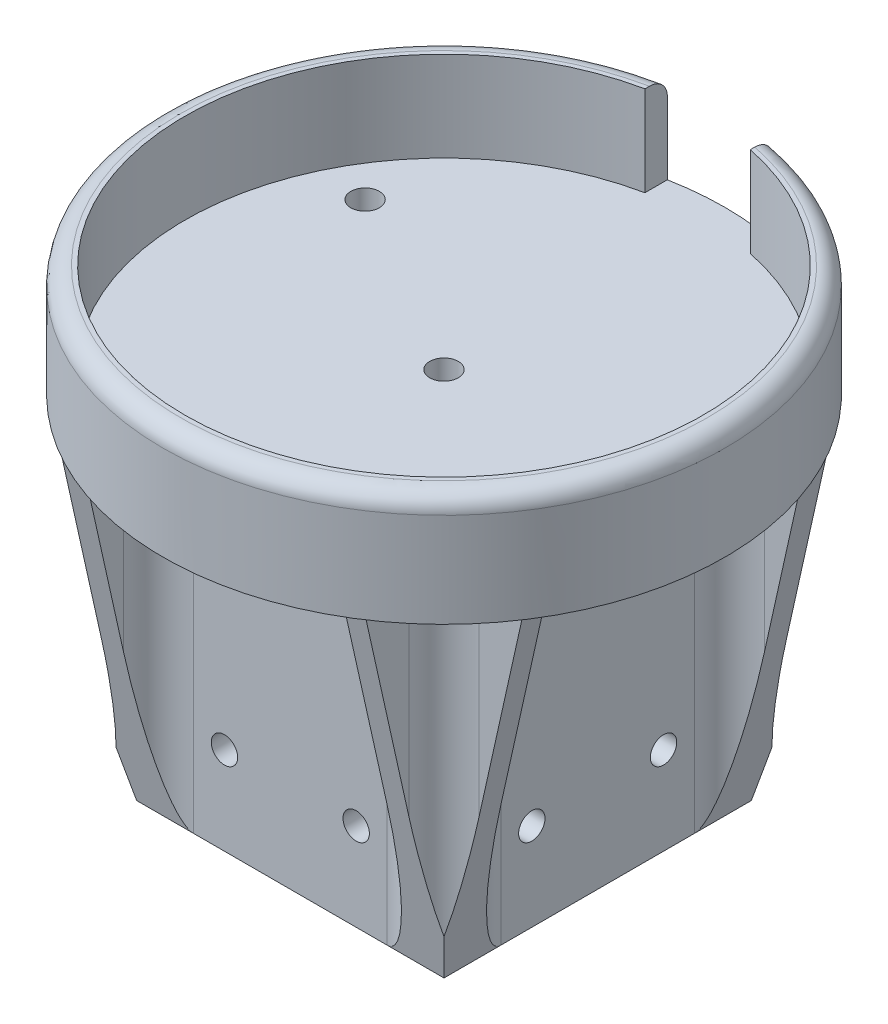
SolidWorks part; units mm, degrees
ref_plane "前视基准面" through (0, 0, 0) normal (0, 0, 1) x (1, 0, 0)
ref_plane "上视基准面" through (0, 0, 0) normal (0, 1, 0) x (1, 0, 0)
ref_plane "右视基准面" through (0, 0, 0) normal (1, 0, 0) x (0, 0, -1)
sketch "草图2" plane through (0, 0, 0) normal (0, 0, 1) x (1, 0, 0)
  line L0 (-64, 5) -> (-64, 21.5)
  line L1 (0, 0) -> (-64, 0)
  line L2 (0, 0) -> (0, 5)
  line L3 (0, 5) -> (-59, 5)
  line L4 (-64, 0) -> (-64, 5)
  line L5 (-60, 25.5) -> (-59, 25.5)
  line L6 (-59, 25.5) -> (-59, 5)
  arc A0 (-64, 21.5) -> (-60, 25.5) centre (-60, 21.5) cw
  point P10 (-64, 25.5)
  dimension "D7" = 4
  dimension "D1" = 5
  dimension "D2" = 20.5
  dimension "D3" = 5
  dimension "D4" = 5
  dimension "D5" = 59
  dimension "D6" = 5
revolve "旋转1" add sketch "草图2" angle 360 about L2
sketch "草图3" plane through (0, 0, 0) normal (0, -1, 0) x (1, 0, 0)
  line L6 (-35, -35) -> (35, -35)
  line L44 (-35, -35) -> (-35, 35)
  line L45 (-35, 35) -> (35, 35)
  line L69 (35, -35) -> (35, 35)
  line L70 (-35, -35) -> (35, 35) construction
  line L71 (-35, 35) -> (35, -35) construction
  point P1 (0, 0)
  dimension "D1" = 70
  dimension "D2" = 70
extrude "凸台-拉伸2" add sketch "草图3" along normal blind 80
sketch "草图5" plane through (0, -80, 0) normal (0, -1, 0) x (1, 0, 0)
  line L1 (-30, -30) -> (30, -30)
  line L2 (-30, -30) -> (-30, 30)
  line L3 (-30, 30) -> (30, 30)
  line L4 (30, -30) -> (30, 30)
  line L5 (-30, -30) -> (30, 30) construction
  line L6 (-30, 30) -> (30, -30) construction
  point P0 (0, 0)
  dimension "D1" = 60
  dimension "D2" = 60
extrude "切除-拉伸2" cut sketch "草图5" against normal blind 80
sketch "草图6" plane through (0, 5, 0) normal (0, 1, 0) x (1, 0, 0)
  circle A0 centre (0, 0) radius 3.25
  circle A1 centre (0, -49.1) radius 3.25
  circle A4 centre (-42.5218, 24.55) radius 3.25
  circle A5 centre (42.5218, 24.55) radius 3.25
  point P11 (1.5088, -2.6133)
  point P12 (0, 0)
  dimension "D1" = 6.5
  dimension "D2" = 6.5
  dimension "D3" = 49.1
extrude "切除-拉伸3" cut sketch "草图6" against normal blind 80
sketch "草图7" plane through (0, 0, 35) normal (0, 0, 1) x (1, 0, 0)
  line L0 (-35, -80) -> (-35, 0) construction
  line L1 (35, -80) -> (-35, -80) construction
  line L2 (35, 0) -> (-35, 0) construction
  line L3 (0, -58.025) -> (0, 58.025) construction
  circle A0 centre (-15, -60) radius 3
  circle A1 centre (-15, -15) radius 3
  circle A2 centre (15, -15) radius 3
  circle A3 centre (15, -60) radius 3
  point P6 (0, 0)
  dimension "D1" = 6
  dimension "D2" = 6
  dimension "D3" = 20
  dimension "D4" = 20
  dimension "D5" = 20
  dimension "D6" = 15
extrude "切除-拉伸4" cut sketch "草图7" against normal through all both and the other way through all
sketch "草图13" plane through (0, 0, -35) normal (0, 0, -1) x (-1, 0, 0)
  line L0 (-35, -80) -> (-52.8448, 0)
  line L1 (-64, 0) -> (64, 0) construction
  point P5 (-52.8448, 0)
rib "筋13" sketch "草图13" sketch "草图13" thickness 5 extrusion direction parallel to sketch draft on no parameters "D1"=5
mirror "镜向2" about plane through (0, 0, 0) normal (0, 0, 1) of "筋13"
pattern_circular "阵列(圆周)1" count 4 over 360 about axis through (0, 0, 0) along (0, 1, 0) of "镜向2", "筋13"
sketch "草图15" plane through (0, 5, 0) normal (0, 1, 0) x (1, 0, 0)
  line L1 (-12, 34.845) -> (12, 34.845)
  line L2 (-12, 34.845) -> (-12, 74.2724)
  line L3 (-12, 74.2724) -> (12, 74.2724)
  line L4 (12, 34.845) -> (12, 74.2724)
  line L5 (-12, 34.845) -> (12, 74.2724) construction
  line L6 (-12, 74.2724) -> (12, 34.845) construction
  point P0 (0, 54.5587)
  point P5 (0, 54.5587)
  dimension "D1" = 24
extrude "切除-拉伸5" cut sketch "草图15" along normal through all
fillet "圆角2" radius 8 12 edges at (35, -40, -30) (35, -40, 30) (30, -40, -35) (35, -40, -35) (-35, -40, -30) (-30, -40, 35) (-30, -40, -35) (-35, -40, -35) (-35, -40, 30) (-35, -40, 35) (30, -40, 35) (35, -40, 35)
pattern_circular "阵列(圆周)2" count 4 over 360 about axis through (0, 0, 0) along (0, -1, 0) of "切除-拉伸4"
